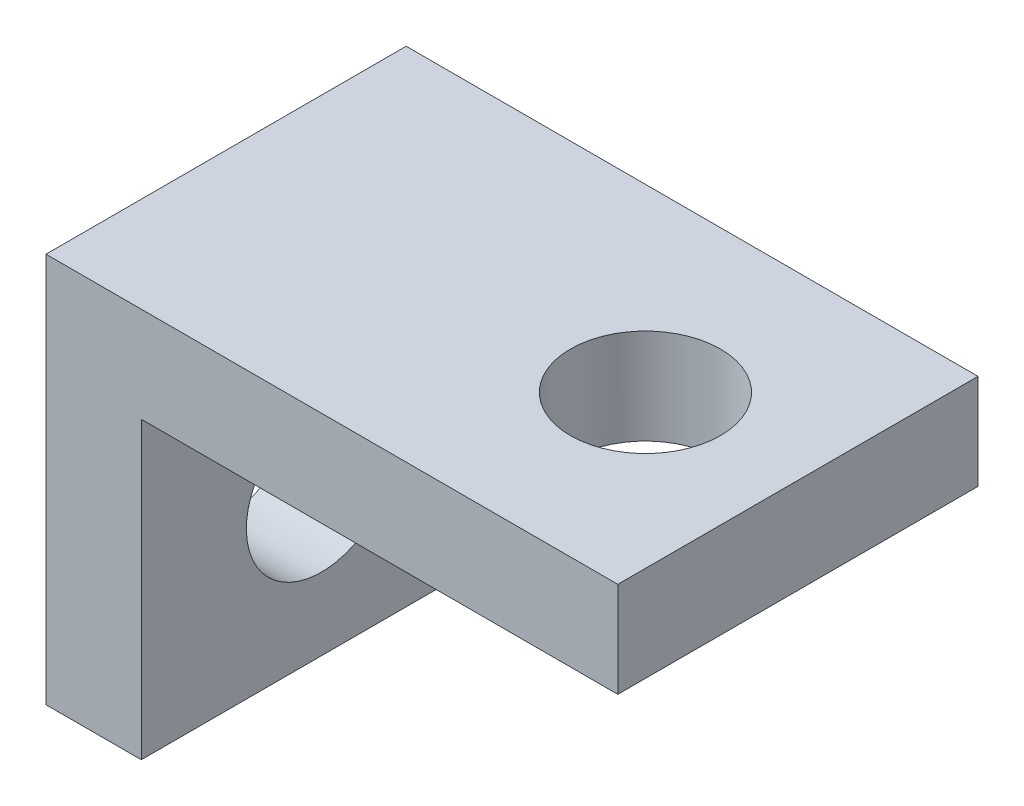
SolidWorks part; units mm, degrees
ref_plane "Front Plane" through (0, 0, 0) normal (0, 0, 1) x (1, 0, 0)
ref_plane "Top Plane" through (0, 0, 0) normal (0, 1, 0) x (1, 0, 0)
ref_plane "Right Plane" through (0, 0, 0) normal (1, 0, 0) x (0, 0, -1)
sketch "Sketch1" plane through (0, 0, 0) normal (0, 0, 1) x (1, 0, 0)
  line L1 (-0.381, -3.9917) -> (1.2065, -3.9917)
  line L2 (-0.381, -3.9917) -> (-0.381, 2.5083)
  line L3 (-0.381, 2.5083) -> (1.2065, 2.5083)
  line L4 (1.2065, -3.9917) -> (1.2065, 2.5083)
  line L5 (1.2065, 2.5083) -> (9.144, 2.5083)
  line L6 (1.2065, 2.5083) -> (1.2065, 0.9208)
  line L7 (1.2065, 0.9208) -> (9.144, 0.9208)
  line L8 (9.144, 2.5083) -> (9.144, 0.9208)
  dimension "D1" = 1.5875
  dimension "D2" = 1.5875
  dimension "D3" = 9.525
  dimension "D4" = 6.5
extrude "Boss-Extrude1" add sketch "Sketch1" along normal blind 6 contours L1 L4 L3 L2 | L8 L5 L4 L7 region at (0.4128, -0.7417, 0) region at (5.1753, 1.7145, 0)
sketch "Sketch2" plane through (1.2065, 0, 0) normal (1, 0, 0) x (0, 0, -1)
  circle A0 centre (-3, -1.5355) radius 1.25
  dimension "D1" = 2.5
extrude "Cut-Extrude1" cut sketch "Sketch2" against normal blind 6
sketch "Sketch3" plane through (0, 0.9208, 0) normal (0, -1, 0) x (1, 0, 0)
  line L0 (9.144, 6) -> (9.144, 0) construction
  circle A0 centre (6.604, 3) radius 1.25
  dimension "D1" = 2.5
  dimension "D2" = 2.54
extrude "Cut-Extrude2" cut sketch "Sketch3" against normal blind 6
equation "\"8mmm\"=1"
